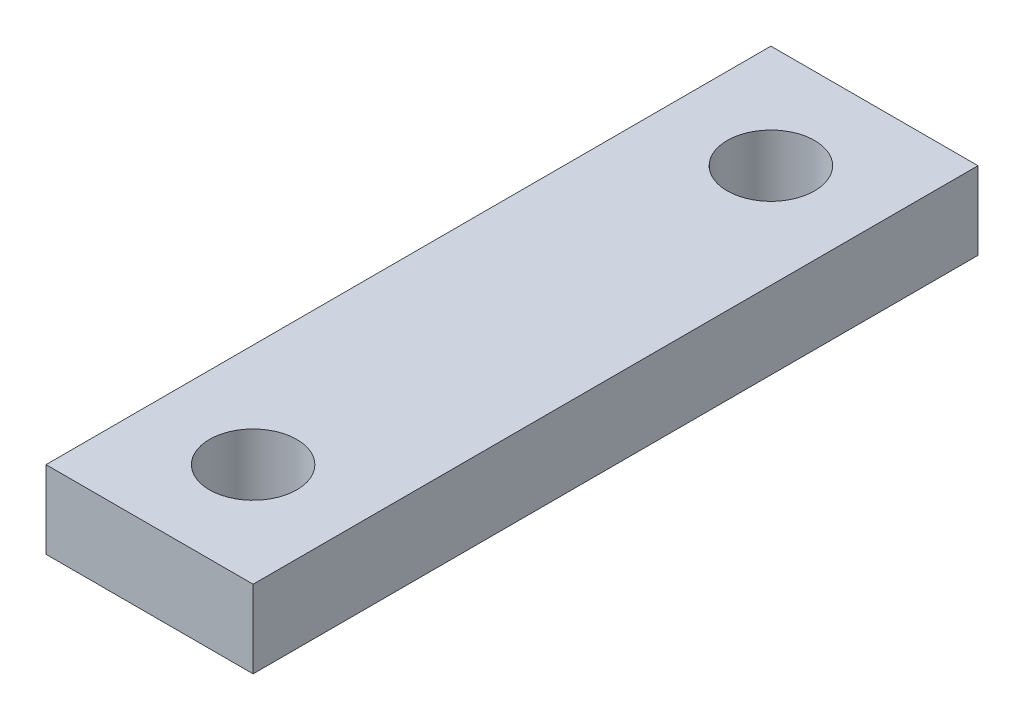
SolidWorks part; units mm, degrees
material "Alloy Steel"
ref_plane "Front Plane" through (0, 0, 0) normal (0, 0, 1) x (1, 0, 0)
ref_plane "Top Plane" through (0, 0, 0) normal (0, 1, 0) x (1, 0, 0)
ref_plane "Right Plane" through (0, 0, 0) normal (1, 0, 0) x (0, 0, -1)
sketch "Sketch1" plane through (0, 0, 0) normal (0, 0, 1) x (1, 0, 0)
  line L1 (-12.7, -4.7625) -> (12.7, -4.7625)
  line L2 (-12.7, -4.7625) -> (-12.7, 4.7625)
  line L3 (-12.7, 4.7625) -> (12.7, 4.7625)
  line L4 (12.7, -4.7625) -> (12.7, 4.7625)
  line L5 (-12.7, -4.7625) -> (12.7, 4.7625) construction
  line L6 (-12.7, 4.7625) -> (12.7, -4.7625) construction
  point P0 (0, 0)
  dimension "D1" = 25.4
  dimension "D2" = 9.525
extrude "Extrude1" add sketch "Sketch1" along normal mid plane 88.9
sketch "Sketch2" plane through (0, 4.7625, 0) normal (0, 1, 0) x (1, 0, 0)
  line L0 (0, 44.45) -> (0, 31.75) construction
  line L1 (12.7, 44.45) -> (-12.7, 44.45) construction
  dimension "D1" = 12.7
hole_wizard "Tap Drill for 1/2-13 Tap1" positions "3DSketch1" profile "Sketch4" hole size "1/2-13" standard "Ansi Inch" end condition through all
sketch3d "3DSketch1"
  point P0 (0, 4.7625, -31.75)
sketch "Sketch4" plane through (0, 4.7625, -31.75) normal (1, 0, 0) x (0, 0, 1)
  line L0 (0, 0) -> (0, 9.525)
  line L1 (0, 9.525) -> (5.3581, 9.525)
  line L2 (5.3581, 9.525) -> (5.3581, 0)
  line L5 (5.3581, 0) -> (0, 0)
  line L11 (0, -6.35) -> (0, 107.95) construction
  dimension "Thru Hole Dia." = 10.7163
  dimension "Thru Hole Depth" = 9.525
mirror "Mirror1" about plane through (0, 0, 0) normal (0, 0, 1) of "Tap Drill for 1/2-13 Tap1"
